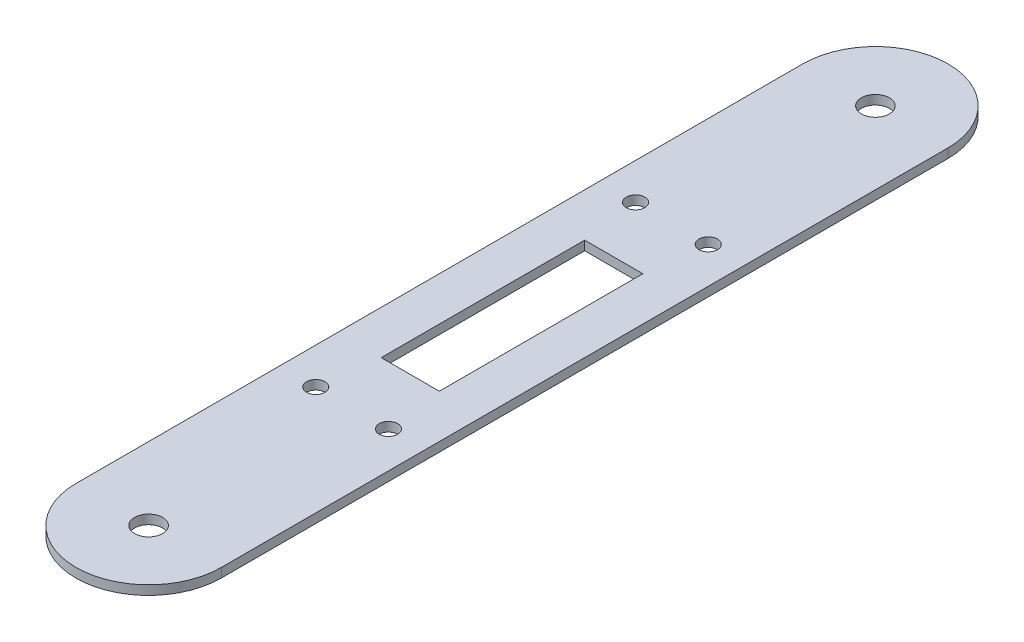
SolidWorks part; units mm, degrees
ref_plane "Front" through (0, 0, 0) normal (0, 0, 1) x (1, 0, 0)
ref_plane "Top" through (0, 0, 0) normal (0, 1, 0) x (1, 0, 0)
ref_plane "Right" through (0, 0, 0) normal (1, 0, 0) x (0, 0, -1)
sketch "Sketch1" plane through (0, 0, 0) normal (0, 1, 0) x (1, 0, 0)
  line L0 (25, 0) -> (25, -300) construction
  line L1 (0, 0) -> (50, 0)
  line L2 (0, 0) -> (0, -300)
  line L3 (0, -300) -> (50, -300)
  line L4 (50, 0) -> (50, -300)
  line L5 (0, -150) -> (50, -150) construction
  line L7 (15, -115) -> (35, -115)
  line L8 (15, -115) -> (15, -185)
  line L9 (15, -185) -> (35, -185)
  line L10 (35, -115) -> (35, -185)
  circle A0 centre (25, -25) radius 4.82
  circle A1 centre (25, -275) radius 4.82
  circle A2 centre (25, -25) radius 25
  circle A3 centre (25, -275) radius 25
  circle A4 centre (12.5, -95) radius 3.175
  circle A5 centre (12.5, -205) radius 3.175
  circle A6 centre (37.5, -95) radius 3.175
  circle A7 centre (37.5, -205) radius 3.175
  dimension "D3" = 9.64
  dimension "D4" = 25
  dimension "D7" = 6.35
  dimension "D9" = 12.5
  dimension "D1" = 50
  dimension "D2" = 300
  dimension "D5" = 70
  dimension "D6" = 20
  dimension "D8" = 55
extrude "Boss-Extrude1" add sketch "Sketch1" along normal blind 3.175 contours A3 L4 A2 L2 | A3 A1 | A2 A0 region at (42.1777, 0, 7.8223) region at (25, 0, 52.5495) region at (25, 0, 250.7071)
